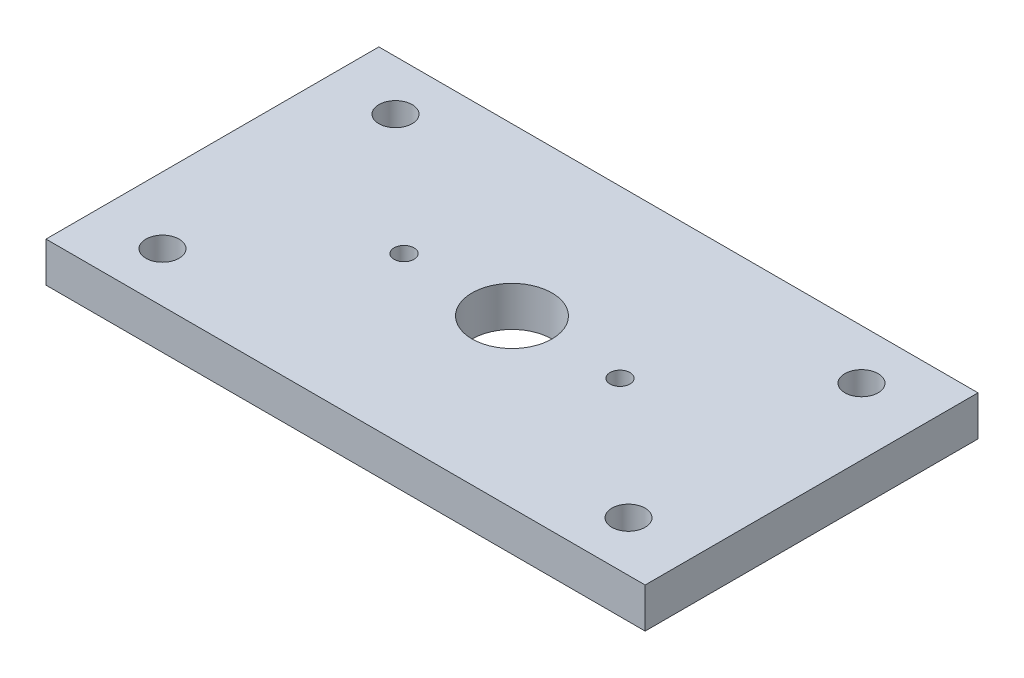
SolidWorks part; units mm, degrees
ref_plane "Front Plane" through (0, 0, 0) normal (0, 0, 1) x (1, 0, 0)
ref_plane "Top Plane" through (0, 0, 0) normal (0, 1, 0) x (1, 0, 0)
ref_plane "Right Plane" through (0, 0, 0) normal (1, 0, 0) x (0, 0, -1)
sketch "Sketch1" plane through (0, 0, 0) normal (0, 1, 0) x (1, 0, 0)
  line L0 (0, -55) -> (0, 55) construction
  line L5 (-55, 0) -> (55, 0) construction
  line L6 (-45, 25) -> (45, 25)
  line L7 (-45, 25) -> (-45, -25)
  line L8 (-45, -25) -> (45, -25)
  line L9 (45, 25) -> (45, -25)
  line L10 (-45, 25) -> (45, -25) construction
  line L11 (-45, -25) -> (45, 25) construction
  circle A0 centre (0, 0) radius 6
  circle A1 centre (0, 0) radius 16.22 construction
  circle A2 centre (-16.22, 0) radius 1.5
  circle A3 centre (16.22, 0) radius 1.5
  circle A4 centre (-35, 17.5) radius 2.5
  circle A5 centre (35, 17.5) radius 2.5
  circle A6 centre (35, -17.5) radius 2.5
  circle A7 centre (-35, -17.5) radius 2.5
  dimension "D1" = 12
  dimension "D2" = 32.44
  dimension "D3" = 3
  dimension "D4" = 5
  dimension "D5" = 50
  dimension "D6" = 35
  dimension "D7" = 90
  dimension "D8" = 17.5
extrude "Boss-Extrude1" add sketch "Sketch1" along normal blind 6
sketch "Sketch2" plane through (0, 0, 0) normal (0, 1, 0) x (1, 0, 0)
  line L0 (0, -3.3) -> (0, 3.3) construction
  line L1 (-3.3, 0) -> (3.3, 0) construction
  circle A0 centre (-35, 17.5) radius 6
  circle A1 centre (35, 17.5) radius 6
  circle A2 centre (35, -17.5) radius 6
  circle A3 centre (-35, -17.5) radius 6
  dimension "D1" = 12
